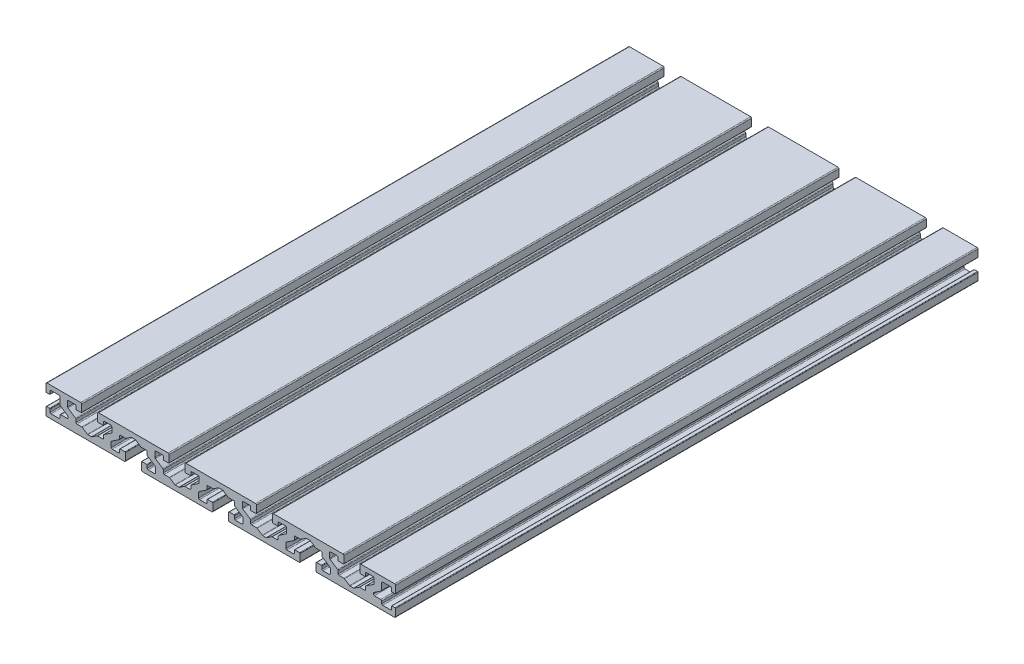
SolidWorks part; units mm, degrees
material "6063-T5"
ref_plane "Front Plane" through (0, 0, 0) normal (0, 0, 1) x (1, 0, 0)
ref_plane "Top Plane" through (0, 0, 0) normal (0, 1, 0) x (1, 0, 0)
ref_plane "Right Plane" through (0, 0, 0) normal (1, 0, 0) x (0, 0, -1)
sketch "Sketch1" plane through (0, 0, 0) normal (0, 0, 1) x (1, 0, 0)
  line L0 (0.5, 0) -> (40.4, 0)
  line L1 (180, 0.5) -> (180, 4.15)
  line L2 (179.5, 15) -> (162.1, 15)
  line L3 (0, 14.5) -> (0, 10.85)
  line L4 (179.75, 4.4) -> (178.15, 4.4)
  line L5 (0.25, 4.4) -> (1.85, 4.4)
  line L6 (179.75, 10.6) -> (178.15, 10.6)
  line L7 (0.25, 10.6) -> (1.85, 10.6)
  line L8 (0, 4.15) -> (0, 0.5)
  line L9 (180, 10.85) -> (180, 14.5)
  line L10 (71.6, 14.5) -> (71.6, 10.85)
  line L11 (18.4, 14.5) -> (18.4, 10.85)
  line L12 (26.6, 14.5) -> (26.6, 10.85)
  line L13 (17.9, 15) -> (0.5, 15)
  line L14 (63.4, 14.5) -> (63.4, 10.85)
  line L15 (116.6, 14.5) -> (116.6, 10.85)
  line L16 (108.4, 14.5) -> (108.4, 10.85)
  line L17 (161.6, 14.5) -> (161.6, 10.85)
  line L18 (153.4, 14.5) -> (153.4, 10.85)
  line L19 (62.9, 15) -> (27.1, 15)
  line L20 (107.9, 15) -> (72.1, 15)
  line L21 (152.9, 15) -> (117.1, 15)
  line L22 (85.9, 0.5) -> (85.9, 4.15)
  line L23 (40.9, 0.5) -> (40.9, 4.15)
  line L24 (49.1, 0.5) -> (49.1, 4.15)
  line L25 (49.6, 0) -> (85.4, 0)
  line L26 (94.1, 0.5) -> (94.1, 4.15)
  line L27 (130.9, 0.5) -> (130.9, 4.15)
  line L28 (139.1, 0.5) -> (139.1, 4.15)
  line L29 (94.6, 0) -> (130.4, 0)
  line L30 (139.6, 0) -> (179.5, 0)
  line L31 (63.15, 10.6) -> (60.65, 10.6)
  line L32 (26.85, 10.6) -> (29.35, 10.6)
  line L33 (18.15, 10.6) -> (15.65, 10.6)
  line L34 (71.85, 10.6) -> (74.35, 10.6)
  line L35 (108.15, 10.6) -> (105.65, 10.6)
  line L36 (116.85, 10.6) -> (119.35, 10.6)
  line L37 (153.15, 10.6) -> (150.65, 10.6)
  line L38 (161.85, 10.6) -> (164.35, 10.6)
  line L39 (40.65, 4.4) -> (38.15, 4.4)
  line L40 (49.35, 4.4) -> (51.85, 4.4)
  line L41 (85.65, 4.4) -> (83.15, 4.4)
  line L42 (94.35, 4.4) -> (96.85, 4.4)
  line L43 (130.65, 4.4) -> (128.15, 4.4)
  line L44 (139.35, 4.4) -> (141.85, 4.4)
  line L45 (52.6, 2.3) -> (55.9, 2.3)
  line L46 (2.6, 2.3) -> (6.6, 2.3)
  line L47 (7.1, 12.2) -> (7.1, 8.7315)
  line L48 (172.9, 12.2) -> (172.9, 8.7315)
  line L49 (6.6, 12.7) -> (2.6, 12.7)
  line L50 (15.4, 10.85) -> (15.4, 12.2)
  line L51 (29.6, 10.85) -> (29.6, 12.2)
  line L52 (74.6, 10.85) -> (74.6, 12.2)
  line L53 (60.4, 10.85) -> (60.4, 12.2)
  line L54 (119.6, 10.85) -> (119.6, 12.2)
  line L55 (105.4, 10.85) -> (105.4, 12.2)
  line L56 (164.6, 10.85) -> (164.6, 12.2)
  line L57 (150.4, 10.85) -> (150.4, 12.2)
  line L58 (37.9, 4.15) -> (37.9, 2.8)
  line L59 (52.1, 4.15) -> (52.1, 2.8)
  line L60 (97.1, 4.15) -> (97.1, 2.8)
  line L61 (82.9, 4.15) -> (82.9, 2.8)
  line L62 (142.1, 4.15) -> (142.1, 2.8)
  line L63 (127.9, 4.15) -> (127.9, 2.8)
  line L64 (56.1, 12.2) -> (56.1, 9.6704)
  line L65 (78.9, 12.2) -> (78.9, 9.6704)
  line L66 (33.9, 12.2) -> (33.9, 9.6704)
  line L67 (30.1, 12.7) -> (33.4, 12.7)
  line L68 (123.6774, 9.2543) -> (119.8226, 6.6845)
  line L69 (21.6056, 2.5) -> (23.3944, 2.5)
  line L70 (11.6, 12.7) -> (14.9, 12.7)
  line L71 (75.1, 12.7) -> (78.4, 12.7)
  line L72 (56.6, 12.7) -> (59.9, 12.7)
  line L73 (120.1, 12.7) -> (123.4, 12.7)
  line L74 (101.6, 12.7) -> (104.9, 12.7)
  line L75 (165.1, 12.7) -> (168.4, 12.7)
  line L76 (146.6, 12.7) -> (149.9, 12.7)
  line L77 (66.6056, 2.5) -> (68.3944, 2.5)
  line L78 (56.3226, 9.2543) -> (60.1774, 6.6845)
  line L79 (101.1, 12.2) -> (101.1, 9.6704)
  line L80 (37.4, 2.3) -> (34.1, 2.3)
  line L81 (97.6, 2.3) -> (100.9, 2.3)
  line L82 (82.4, 2.3) -> (79.1, 2.3)
  line L83 (142.6, 2.3) -> (145.9, 2.3)
  line L84 (127.4, 2.3) -> (124.1, 2.3)
  line L85 (33.6, 2.8) -> (33.6, 5.3296)
  line L86 (56.4, 2.8) -> (56.4, 5.3296)
  line L87 (101.4, 2.8) -> (101.4, 5.3296)
  line L88 (91.1718, 12.416) -> (93.7699, 10.684)
  line L89 (89.1056, 12.5) -> (90.8944, 12.5)
  line L90 (78.8226, 5.7457) -> (82.6774, 8.3155)
  line L91 (168.6774, 9.2543) -> (164.8226, 6.6845)
  line L92 (29.6, 4.9) -> (29.6, 6.2685)
  line L93 (18.4528, 4.4) -> (15.9, 4.4)
  line L94 (26.5472, 4.4) -> (29.1, 4.4)
  line L95 (123.9, 12.2) -> (123.9, 9.6704)
  line L96 (7.3226, 8.3155) -> (11.1774, 5.7457)
  line L97 (15.4, 4.9) -> (15.4, 6.2685)
  line L98 (18.7301, 4.316) -> (21.3282, 2.584)
  line L99 (2.1, 4.15) -> (2.1, 2.8)
  line L100 (2.1, 12.2) -> (2.1, 10.85)
  line L101 (173.4, 12.7) -> (177.4, 12.7)
  line L102 (177.9, 12.2) -> (177.9, 10.85)
  line L103 (173.4, 2.3) -> (177.4, 2.3)
  line L104 (177.9, 2.8) -> (177.9, 4.15)
  line L105 (26.2699, 4.316) -> (23.6718, 2.584)
  line L106 (44.1056, 12.5) -> (45.8944, 12.5)
  line L107 (33.6774, 9.2543) -> (29.8226, 6.6845)
  line L108 (111.6056, 2.5) -> (113.3944, 2.5)
  line L109 (101.3226, 9.2543) -> (105.1774, 6.6845)
  line L110 (146.1, 12.2) -> (146.1, 9.6704)
  line L111 (168.9, 12.2) -> (168.9, 9.6704)
  line L112 (74.6, 4.9) -> (74.6, 6.2685)
  line L113 (156.6056, 2.5) -> (158.3944, 2.5)
  line L114 (97.1, 10.1) -> (97.1, 8.7315)
  line L115 (11.1, 12.2) -> (11.1, 9.6704)
  line L116 (11.3226, 9.2543) -> (15.1774, 6.6845)
  line L117 (146.3226, 9.2543) -> (150.1774, 6.6845)
  line L118 (78.6, 2.8) -> (78.6, 5.3296)
  line L119 (146.4, 2.8) -> (146.4, 5.3296)
  line L120 (33.8226, 5.7457) -> (37.6774, 8.3155)
  line L121 (136.1718, 12.416) -> (138.7699, 10.684)
  line L122 (134.1056, 12.5) -> (135.8944, 12.5)
  line L123 (46.1718, 12.416) -> (48.7699, 10.684)
  line L124 (123.8226, 5.7457) -> (127.6774, 8.3155)
  line L125 (123.6, 2.8) -> (123.6, 5.3296)
  line L126 (78.6774, 9.2543) -> (74.8226, 6.6845)
  line L127 (71.5472, 4.4) -> (74.1, 4.4)
  line L128 (63.4528, 4.4) -> (60.9, 4.4)
  line L129 (60.4, 4.9) -> (60.4, 6.2685)
  line L130 (119.6, 4.9) -> (119.6, 6.2685)
  line L131 (116.5472, 4.4) -> (119.1, 4.4)
  line L132 (108.4528, 4.4) -> (105.9, 4.4)
  line L133 (105.4, 4.9) -> (105.4, 6.2685)
  line L134 (164.6, 4.9) -> (164.6, 6.2685)
  line L135 (161.5472, 4.4) -> (164.1, 4.4)
  line L136 (153.4528, 4.4) -> (150.9, 4.4)
  line L137 (150.4, 4.9) -> (150.4, 6.2685)
  line L138 (63.7301, 4.316) -> (66.3282, 2.584)
  line L139 (71.2699, 4.316) -> (68.6718, 2.584)
  line L140 (108.7301, 4.316) -> (111.3282, 2.584)
  line L141 (116.2699, 4.316) -> (113.6718, 2.584)
  line L142 (153.7301, 4.316) -> (156.3282, 2.584)
  line L143 (161.2699, 4.316) -> (158.6718, 2.584)
  line L144 (11.4, 4.9) -> (11.4, 5.3296)
  line L145 (49.0472, 10.6) -> (51.6, 10.6)
  line L146 (40.9528, 10.6) -> (38.4, 10.6)
  line L147 (37.9, 10.1) -> (37.9, 8.7315)
  line L148 (52.1, 10.1) -> (52.1, 8.7315)
  line L149 (41.2301, 10.684) -> (43.8282, 12.416)
  line L150 (52.3226, 8.3155) -> (56.1774, 5.7457)
  line L151 (94.0472, 10.6) -> (96.6, 10.6)
  line L152 (85.9528, 10.6) -> (83.4, 10.6)
  line L153 (82.9, 10.1) -> (82.9, 8.7315)
  line L154 (142.1, 10.1) -> (142.1, 8.7315)
  line L155 (139.0472, 10.6) -> (141.6, 10.6)
  line L156 (130.9528, 10.6) -> (128.4, 10.6)
  line L157 (127.9, 10.1) -> (127.9, 8.7315)
  line L158 (86.2301, 10.684) -> (88.8282, 12.416)
  line L159 (97.3226, 8.3155) -> (101.1774, 5.7457)
  line L160 (131.2301, 10.684) -> (133.8282, 12.416)
  line L161 (142.3226, 8.3155) -> (146.1774, 5.7457)
  line L162 (7.6, 4.4) -> (10.9, 4.4)
  line L163 (7.1, 3.9) -> (7.1, 2.8)
  line L164 (7.1, 2.3) -> (11.4, 2.3) [skipped]
  line L166 (168.8226, 5.7457) -> (172.6774, 8.3155)
  line L167 (168.6, 4.9) -> (168.6, 5.3296)
  line L170 (172.4, 4.4) -> (169.1, 4.4)
  line L171 (172.9, 3.9) -> (172.9, 2.8)
  line L172 (172.9, 2.3) -> (168.6, 2.3) [skipped]
  line L173 (7.1, 3.9) -> (7.1, 2.3) [skipped]
  line L174 (172.9, 3.9) -> (172.9, 2.3) [skipped]
  arc A0 (0.5, 0) -> (0, 0.5) centre (0.5, 0.5) cw
  arc A1 (0.5, 15) -> (0, 14.5) centre (0.5, 14.5) ccw
  arc A2 (179.5, 0) -> (180, 0.5) centre (179.5, 0.5) ccw
  arc A3 (180, 14.5) -> (179.5, 15) centre (179.5, 14.5) ccw
  arc A4 (161.6, 14.5) -> (162.1, 15) centre (162.1, 14.5) cw
  arc A5 (153.4, 14.5) -> (152.9, 15) centre (152.9, 14.5) ccw
  arc A6 (139.1, 0.5) -> (139.6, 0) centre (139.6, 0.5) ccw
  arc A7 (130.9, 0.5) -> (130.4, 0) centre (130.4, 0.5) cw
  arc A8 (108.4, 14.5) -> (107.9, 15) centre (107.9, 14.5) ccw
  arc A9 (116.6, 14.5) -> (117.1, 15) centre (117.1, 14.5) cw
  arc A10 (85.9, 0.5) -> (85.4, 0) centre (85.4, 0.5) cw
  arc A11 (94.1, 0.5) -> (94.6, 0) centre (94.6, 0.5) ccw
  arc A12 (71.6, 14.5) -> (72.1, 15) centre (72.1, 14.5) cw
  arc A13 (63.4, 14.5) -> (62.9, 15) centre (62.9, 14.5) ccw
  arc A14 (49.6, 0) -> (49.1, 0.5) centre (49.6, 0.5) cw
  arc A15 (40.4, 0) -> (40.9, 0.5) centre (40.4, 0.5) ccw
  arc A16 (17.9, 15) -> (18.4, 14.5) centre (17.9, 14.5) cw
  arc A17 (27.1, 15) -> (26.6, 14.5) centre (27.1, 14.5) ccw
  arc A18 (7.1, 3.9) -> (7.6, 4.4) centre (7.6, 3.9) cw
  arc A19 (10.9, 4.4) -> (11.4, 4.9) centre (10.9, 4.9) ccw
  arc A20 (11.1774, 5.7457) -> (11.4, 5.3296) centre (10.9, 5.3296) cw
  arc A21 (7.3226, 8.3155) -> (7.1, 8.7315) centre (7.6, 8.7315) cw
  arc A22 (2.1, 2.8) -> (2.6, 2.3) centre (2.6, 2.8) ccw
  arc A23 (7.1, 2.8) -> (6.6, 2.3) centre (6.6, 2.8) cw
  arc A24 (7.1, 12.2) -> (6.6, 12.7) centre (6.6, 12.2) ccw
  arc A25 (2.6, 12.7) -> (2.1, 12.2) centre (2.6, 12.2) ccw
  arc A26 (29.6, 12.2) -> (30.1, 12.7) centre (30.1, 12.2) cw
  arc A27 (33.4, 12.7) -> (33.9, 12.2) centre (33.4, 12.2) cw
  arc A28 (33.9, 9.6704) -> (33.6774, 9.2543) centre (33.4, 9.6704) cw
  arc A29 (29.6, 6.2685) -> (29.8226, 6.6845) centre (30.1, 6.2685) cw
  arc A30 (29.1, 4.4) -> (29.6, 4.9) centre (29.1, 4.9) ccw
  arc A31 (26.5472, 4.4) -> (26.2699, 4.316) centre (26.5472, 3.9) ccw
  arc A32 (23.3944, 2.5) -> (23.6718, 2.584) centre (23.3944, 3) ccw
  arc A33 (21.6056, 2.5) -> (21.3282, 2.584) centre (21.6056, 3) cw
  arc A34 (18.4528, 4.4) -> (18.7301, 4.316) centre (18.4528, 3.9) cw
  arc A35 (15.9, 4.4) -> (15.4, 4.9) centre (15.9, 4.9) cw
  arc A36 (15.4, 6.2685) -> (15.1774, 6.6845) centre (14.9, 6.2685) ccw
  arc A37 (11.1, 9.6704) -> (11.3226, 9.2543) centre (11.6, 9.6704) ccw
  arc A38 (11.6, 12.7) -> (11.1, 12.2) centre (11.6, 12.2) ccw
  arc A39 (14.9, 12.7) -> (15.4, 12.2) centre (14.9, 12.2) cw
  arc A40 (52.1, 2.8) -> (52.6, 2.3) centre (52.6, 2.8) ccw
  arc A41 (55.9, 2.3) -> (56.4, 2.8) centre (55.9, 2.8) ccw
  arc A42 (56.4, 5.3296) -> (56.1774, 5.7457) centre (55.9, 5.3296) ccw
  arc A43 (52.1, 8.7315) -> (52.3226, 8.3155) centre (52.6, 8.7315) ccw
  arc A44 (51.6, 10.6) -> (52.1, 10.1) centre (51.6, 10.1) cw
  arc A45 (48.7699, 10.684) -> (49.0472, 10.6) centre (49.0472, 11.1) ccw
  arc A46 (45.8944, 12.5) -> (46.1718, 12.416) centre (45.8944, 12) cw
  arc A47 (44.1056, 12.5) -> (43.8282, 12.416) centre (44.1056, 12) ccw
  arc A48 (41.2301, 10.684) -> (40.9528, 10.6) centre (40.9528, 11.1) cw
  arc A49 (38.4, 10.6) -> (37.9, 10.1) centre (38.4, 10.1) ccw
  arc A50 (37.9, 8.7315) -> (37.6774, 8.3155) centre (37.4, 8.7315) cw
  arc A51 (33.6, 5.3296) -> (33.8226, 5.7457) centre (34.1, 5.3296) cw
  arc A52 (34.1, 2.3) -> (33.6, 2.8) centre (34.1, 2.8) cw
  arc A53 (37.9, 2.8) -> (37.4, 2.3) centre (37.4, 2.8) cw
  arc A54 (60.4, 6.2685) -> (60.1774, 6.6845) centre (59.9, 6.2685) ccw
  arc A55 (60.9, 4.4) -> (60.4, 4.9) centre (60.9, 4.9) cw
  arc A56 (63.4528, 4.4) -> (63.7301, 4.316) centre (63.4528, 3.9) cw
  arc A57 (66.6056, 2.5) -> (66.3282, 2.584) centre (66.6056, 3) cw
  arc A58 (68.6718, 2.584) -> (68.3944, 2.5) centre (68.3944, 3) cw
  arc A59 (71.5472, 4.4) -> (71.2699, 4.316) centre (71.5472, 3.9) ccw
  arc A60 (74.6, 4.9) -> (74.1, 4.4) centre (74.1, 4.9) cw
  arc A61 (74.6, 6.2685) -> (74.8226, 6.6845) centre (75.1, 6.2685) cw
  arc A62 (78.9, 9.6704) -> (78.6774, 9.2543) centre (78.4, 9.6704) cw
  arc A63 (78.9, 12.2) -> (78.4, 12.7) centre (78.4, 12.2) ccw
  arc A64 (74.6, 12.2) -> (75.1, 12.7) centre (75.1, 12.2) cw
  arc A65 (56.1, 9.6704) -> (56.3226, 9.2543) centre (56.6, 9.6704) ccw
  arc A66 (56.1, 12.2) -> (56.6, 12.7) centre (56.6, 12.2) cw
  arc A67 (60.4, 12.2) -> (59.9, 12.7) centre (59.9, 12.2) ccw
  arc A68 (119.6, 12.2) -> (120.1, 12.7) centre (120.1, 12.2) cw
  arc A69 (123.4, 12.7) -> (123.9, 12.2) centre (123.4, 12.2) cw
  arc A70 (123.9, 9.6704) -> (123.6774, 9.2543) centre (123.4, 9.6704) cw
  arc A71 (119.6, 6.2685) -> (119.8226, 6.6845) centre (120.1, 6.2685) cw
  arc A72 (119.6, 4.9) -> (119.1, 4.4) centre (119.1, 4.9) cw
  arc A73 (116.5472, 4.4) -> (116.2699, 4.316) centre (116.5472, 3.9) ccw
  arc A74 (113.6718, 2.584) -> (113.3944, 2.5) centre (113.3944, 3) cw
  arc A75 (111.6056, 2.5) -> (111.3282, 2.584) centre (111.6056, 3) cw
  arc A76 (108.4528, 4.4) -> (108.7301, 4.316) centre (108.4528, 3.9) cw
  arc A77 (105.9, 4.4) -> (105.4, 4.9) centre (105.9, 4.9) cw
  arc A78 (105.4, 6.2685) -> (105.1774, 6.6845) centre (104.9, 6.2685) ccw
  arc A79 (101.1, 9.6704) -> (101.3226, 9.2543) centre (101.6, 9.6704) ccw
  arc A80 (101.6, 12.7) -> (101.1, 12.2) centre (101.6, 12.2) ccw
  arc A81 (105.4, 12.2) -> (104.9, 12.7) centre (104.9, 12.2) ccw
  arc A82 (82.9, 8.7315) -> (82.6774, 8.3155) centre (82.4, 8.7315) cw
  arc A83 (78.8226, 5.7457) -> (78.6, 5.3296) centre (79.1, 5.3296) ccw
  arc A84 (78.6, 2.8) -> (79.1, 2.3) centre (79.1, 2.8) ccw
  arc A85 (82.9, 2.8) -> (82.4, 2.3) centre (82.4, 2.8) cw
  arc A86 (97.1, 2.8) -> (97.6, 2.3) centre (97.6, 2.8) ccw
  arc A87 (101.4, 2.8) -> (100.9, 2.3) centre (100.9, 2.8) cw
  arc A88 (101.4, 5.3296) -> (101.1774, 5.7457) centre (100.9, 5.3296) ccw
  arc A89 (97.1, 8.7315) -> (97.3226, 8.3155) centre (97.6, 8.7315) ccw
  arc A90 (97.1, 10.1) -> (96.6, 10.6) centre (96.6, 10.1) ccw
  arc A91 (94.0472, 10.6) -> (93.7699, 10.684) centre (94.0472, 11.1) cw
  arc A92 (91.1718, 12.416) -> (90.8944, 12.5) centre (90.8944, 12) ccw
  arc A93 (89.1056, 12.5) -> (88.8282, 12.416) centre (89.1056, 12) ccw
  arc A94 (85.9528, 10.6) -> (86.2301, 10.684) centre (85.9528, 11.1) ccw
  arc A95 (83.4, 10.6) -> (82.9, 10.1) centre (83.4, 10.1) ccw
  arc A96 (164.6, 12.2) -> (165.1, 12.7) centre (165.1, 12.2) cw
  arc A97 (168.4, 12.7) -> (168.9, 12.2) centre (168.4, 12.2) cw
  arc A98 (168.9, 9.6704) -> (168.6774, 9.2543) centre (168.4, 9.6704) cw
  arc A99 (164.6, 6.2685) -> (164.8226, 6.6845) centre (165.1, 6.2685) cw
  arc A100 (164.6, 4.9) -> (164.1, 4.4) centre (164.1, 4.9) cw
  arc A101 (161.5472, 4.4) -> (161.2699, 4.316) centre (161.5472, 3.9) ccw
  arc A102 (158.6718, 2.584) -> (158.3944, 2.5) centre (158.3944, 3) cw
  arc A103 (156.6056, 2.5) -> (156.3282, 2.584) centre (156.6056, 3) cw
  arc A104 (153.4528, 4.4) -> (153.7301, 4.316) centre (153.4528, 3.9) cw
  arc A105 (150.9, 4.4) -> (150.4, 4.9) centre (150.9, 4.9) cw
  arc A106 (150.4, 6.2685) -> (150.1774, 6.6845) centre (149.9, 6.2685) ccw
  arc A107 (146.1, 9.6704) -> (146.3226, 9.2543) centre (146.6, 9.6704) ccw
  arc A108 (146.6, 12.7) -> (146.1, 12.2) centre (146.6, 12.2) ccw
  arc A109 (150.4, 12.2) -> (149.9, 12.7) centre (149.9, 12.2) ccw
  arc A110 (142.1, 2.8) -> (142.6, 2.3) centre (142.6, 2.8) ccw
  arc A111 (145.9, 2.3) -> (146.4, 2.8) centre (145.9, 2.8) ccw
  arc A112 (146.4, 5.3296) -> (146.1774, 5.7457) centre (145.9, 5.3296) ccw
  arc A113 (142.1, 8.7315) -> (142.3226, 8.3155) centre (142.6, 8.7315) ccw
  arc A114 (142.1, 10.1) -> (141.6, 10.6) centre (141.6, 10.1) ccw
  arc A115 (139.0472, 10.6) -> (138.7699, 10.684) centre (139.0472, 11.1) cw
  arc A116 (136.1718, 12.416) -> (135.8944, 12.5) centre (135.8944, 12) ccw
  arc A117 (134.1056, 12.5) -> (133.8282, 12.416) centre (134.1056, 12) ccw
  arc A118 (130.9528, 10.6) -> (131.2301, 10.684) centre (130.9528, 11.1) ccw
  arc A119 (128.4, 10.6) -> (127.9, 10.1) centre (128.4, 10.1) ccw
  arc A120 (127.9, 8.7315) -> (127.6774, 8.3155) centre (127.4, 8.7315) cw
  arc A121 (123.8226, 5.7457) -> (123.6, 5.3296) centre (124.1, 5.3296) ccw
  arc A122 (124.1, 2.3) -> (123.6, 2.8) centre (124.1, 2.8) cw
  arc A123 (127.9, 2.8) -> (127.4, 2.3) centre (127.4, 2.8) cw
  arc A124 (172.6774, 8.3155) -> (172.9, 8.7315) centre (172.4, 8.7315) ccw
  arc A125 (168.8226, 5.7457) -> (168.6, 5.3296) centre (169.1, 5.3296) ccw
  arc A126 (169.1, 4.4) -> (168.6, 4.9) centre (169.1, 4.9) cw
  arc A127 (172.9, 3.9) -> (172.4, 4.4) centre (172.4, 3.9) ccw
  arc A128 (172.9, 2.8) -> (173.4, 2.3) centre (173.4, 2.8) ccw
  arc A129 (177.4, 2.3) -> (177.9, 2.8) centre (177.4, 2.8) ccw
  arc A130 (172.9, 12.2) -> (173.4, 12.7) centre (173.4, 12.2) cw
  arc A131 (177.4, 12.7) -> (177.9, 12.2) centre (177.4, 12.2) cw
  arc A132 (119.35, 10.6) -> (119.6, 10.85) centre (119.35, 10.85) ccw
  arc A133 (116.6, 10.85) -> (116.85, 10.6) centre (116.85, 10.85) ccw
  arc A134 (108.4, 10.85) -> (108.15, 10.6) centre (108.15, 10.85) cw
  arc A135 (105.65, 10.6) -> (105.4, 10.85) centre (105.65, 10.85) cw
  arc A136 (96.85, 4.4) -> (97.1, 4.15) centre (96.85, 4.15) cw
  arc A137 (94.1, 4.15) -> (94.35, 4.4) centre (94.35, 4.15) cw
  arc A138 (85.65, 4.4) -> (85.9, 4.15) centre (85.65, 4.15) cw
  arc A139 (82.9, 4.15) -> (83.15, 4.4) centre (83.15, 4.15) cw
  arc A140 (74.35, 10.6) -> (74.6, 10.85) centre (74.35, 10.85) ccw
  arc A141 (71.6, 10.85) -> (71.85, 10.6) centre (71.85, 10.85) ccw
  arc A142 (63.4, 10.85) -> (63.15, 10.6) centre (63.15, 10.85) cw
  arc A143 (60.65, 10.6) -> (60.4, 10.85) centre (60.65, 10.85) cw
  arc A144 (51.85, 4.4) -> (52.1, 4.15) centre (51.85, 4.15) cw
  arc A145 (49.1, 4.15) -> (49.35, 4.4) centre (49.35, 4.15) cw
  arc A146 (40.9, 4.15) -> (40.65, 4.4) centre (40.65, 4.15) ccw
  arc A147 (38.15, 4.4) -> (37.9, 4.15) centre (38.15, 4.15) ccw
  arc A148 (29.35, 10.6) -> (29.6, 10.85) centre (29.35, 10.85) ccw
  arc A149 (26.6, 10.85) -> (26.85, 10.6) centre (26.85, 10.85) ccw
  arc A150 (18.4, 10.85) -> (18.15, 10.6) centre (18.15, 10.85) cw
  arc A151 (15.65, 10.6) -> (15.4, 10.85) centre (15.65, 10.85) cw
  arc A152 (0, 4.15) -> (0.25, 4.4) centre (0.25, 4.15) cw
  arc A153 (1.85, 4.4) -> (2.1, 4.15) centre (1.85, 4.15) cw
  arc A154 (1.85, 10.6) -> (2.1, 10.85) centre (1.85, 10.85) ccw
  arc A155 (0, 10.85) -> (0.25, 10.6) centre (0.25, 10.85) ccw
  arc A156 (178.15, 4.4) -> (177.9, 4.15) centre (178.15, 4.15) ccw
  arc A157 (179.75, 4.4) -> (180, 4.15) centre (179.75, 4.15) cw
  arc A158 (179.75, 10.6) -> (180, 10.85) centre (179.75, 10.85) ccw
  arc A159 (178.15, 10.6) -> (177.9, 10.85) centre (178.15, 10.85) cw
  arc A160 (164.35, 10.6) -> (164.6, 10.85) centre (164.35, 10.85) ccw
  arc A161 (161.6, 10.85) -> (161.85, 10.6) centre (161.85, 10.85) ccw
  arc A162 (153.4, 10.85) -> (153.15, 10.6) centre (153.15, 10.85) cw
  arc A163 (150.65, 10.6) -> (150.4, 10.85) centre (150.65, 10.85) cw
  arc A164 (141.85, 4.4) -> (142.1, 4.15) centre (141.85, 4.15) cw
  arc A165 (139.1, 4.15) -> (139.35, 4.4) centre (139.35, 4.15) cw
  arc A166 (130.9, 4.15) -> (130.65, 4.4) centre (130.65, 4.15) ccw
  arc A167 (128.15, 4.4) -> (127.9, 4.15) centre (128.15, 4.15) ccw
  point P228 (7.1, 2.3)
  dimension "D3" = 2
  dimension "D1" = 2
  dimension "D4" = 3
  dimension "D2" = 3
extrude "Boss-Extrude1" add sketch "Sketch1" along normal blind 300 contours L19 A17 L12 A149 L32 A148 L51 A26 L67 A27 L66 A28 L107 A29 L92 A30 L94 A31 L105 A32 L69 A33 L98 A34 L93 A35 L97 A36 L116 A37 L115 A38 L70 A39 L50 A151 L33 A150 L11 A16 L13 A1 L3 A155 L7 A154 L100 A25 L49 A24 L47 A21 L96 A20 L144 A19 L162 A18 L163 A23 L46 A22 L99 A153 L5 A152 L8 A0 L0 A15 L23 A146 L39 A147 L58 A53 L80 A52 L85 A51 L120 A50 L147 A49 L146 A48 L149 A47 L106 A46 L123 A45 L145 A44 L148 A43 L150 A42 L86 A41 L45 A40 L59 A144 L40 A145 L24 A14 L25 A10 L22 A138 L41 A139 L61 A85 L82 A84 L118 A83 L90 A82 L153 A95 L152 A94 L158 A93 L89 A92 L88 A91 L151 A90 L114 A89 L159 A88 L87 A87 L81 A86 L60 A136 L42 A137 L26 A11 L29 A7 L27 A166 L43 A167 L63 A123 L84 A122 L125 A121 L124 A120 L157 A119 L156 A118 L160 A117 L122 A116 L121 A115 L155 A114 L154 A113 L161 A112 L119 A111 L83 A110 L62 A164 L44 A165 L28 A6 L30 A2 L1 A157 L4 A156 L104 A129 L103 A128 L171 A127 L170 A126 L167 A125 L166 A124 L48 A130 L101 A131 L102 A159 L6 A158 L9 A3 L2 A4 L17 A161 L38 A160 L56 A96 L75 A97 L111 A98 L91 A99 L134 A100 L135 A101 L143 A102 L113 A103 L142 A104 L136 A105 L137 A106 L117 A107 L110 A108 L76 A109 L57 A163 L37 A162 L18 A5 L21 A9 L15 A133 L36 A132 L54 A68 L73 A69 L95 A70 L68 A71 L130 A72 L131 A73 L141 A74 L108 A75 L140 A76 L132 A77 L133 A78 L109 A79 L79 A80 L74 A81 L55 A135 L35 A134 L16 A8 L20 A12 L10 A141 L34 A140 L52 A64 L71 A63 L65 A62 L126 A61 L112 A60 L127 A59 L139 A58 L77 A57 L138 A56 L128 A55 L129 A54 L78 A65 L64 A66 L72 A67 L53 A143 L31 A142 L14 A13
